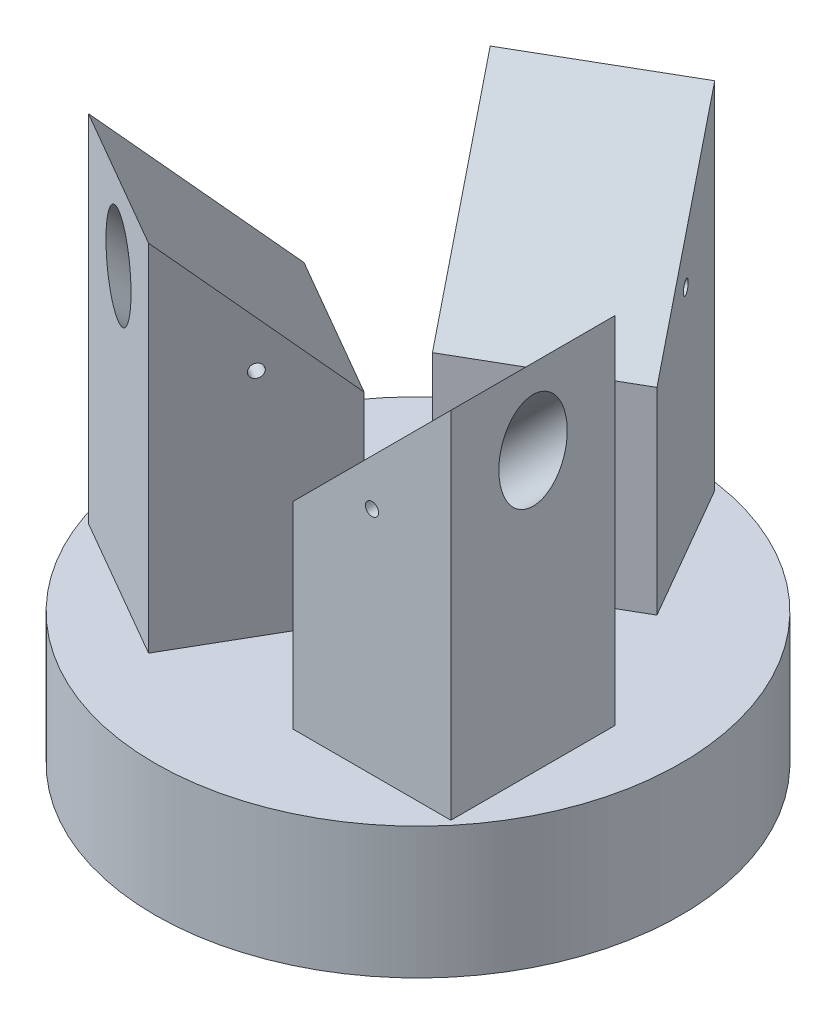
SolidWorks part; units mm, degrees
ref_plane "Front Plane" through (0, 0, 0) normal (0, 0, 1) x (1, 0, 0)
ref_plane "Top Plane" through (0, 0, 0) normal (0, 1, 0) x (1, 0, 0)
ref_plane "Right Plane" through (0, 0, 0) normal (1, 0, 0) x (0, 0, -1)
sketch "Sketch1" plane through (0, 0, 0) normal (0, 1, 0) x (1, 0, 0)
  circle A0 centre (0, 0) radius 50.8
  dimension "D1" = 101.6
extrude "Boss-Extrude1" add sketch "Sketch1" along normal blind 25.4
ref_axis "Axis1" through (0, 25.4, 0) along (0, -1, 0)
sketch "Sketch3" plane through (0, 25.4, 0) normal (0, 1, 0) x (1, 0, 0)
  line L0 (0, 0) -> (50.8, 0)
  circle A0 centre (0, 0) radius 50.8 construction
ref_plane "Plane1" through (0, 0, 0) normal (0, 0, 1) x (1, 0, 0)
sketch "Sketch4" plane through (0, 0, 0) normal (0, 0, 1) x (1, 0, 0)
  line L0 (7.62, 25.4) -> (7.62, 63.5)
  line L1 (38.1, 25.4) -> (7.62, 25.4)
  line L2 (38.1, 25.4) -> (38.1, 93.98)
  line L3 (38.1, 93.98) -> (7.62, 63.5)
  line L4 (7.62, 63.5) -> (52.1327, 63.5) construction
  dimension "D1" = 45
extrude "Boss-Extrude2" add sketch "Sketch4" along normal blind 31.75
sketch "Sketch5" plane through (38.1, 0, 0) normal (1, 0, 0) x (0, 0, -1)
  line L0 (-15.875, 93.98) -> (-15.875, 81.28) construction
  line L1 (-31.75, 93.98) -> (0, 93.98) construction
  line L2 (-15.875, 95.504) -> (-2.6499, 95.504)
  circle A0 centre (-15.875, 81.28) radius 14.224
  dimension "D1" = 12.7
ref_plane "Plane2" through (66.802, 66.802, 0) normal (0.7071, 0.7071, 0) x (0, 0, -1)
sketch "Sketch7" plane through (7.62, 0, 0) normal (-1, 0, 0) x (0, 0, 1)
  line L0 (15.875, 63.5) -> (15.875, 50.8) construction
  line L1 (31.75, 63.5) -> (0, 63.5) construction
  line L3 (15.875, 57.404) -> (28.7041, 57.404)
  circle A0 centre (15.875, 50.8) radius 6.604
  dimension "D1" = 12.7
ref_plane "Plane3" through (32.512, 32.512, 0) normal (-0.7071, -0.7071, 0) x (0, 0, 1)
sketch "Sketch9" plane through (66.802, 66.802, 0) normal (0.7071, 0.7071, 0) x (0, 0, -1)
  line L0 (-15.875, 40.5908) -> (-15.875, 29.1608) construction
  circle A0 centre (-15.875, 29.1608) radius 6.604
  dimension "D1" = 11.43
extrude "Cut-Extrude2" cut sketch "Sketch9" against normal blind 68.58
sketch "Sketch10" plane through (0, 0, 31.75) normal (0, 0, 1) x (1, 0, 0)
  line L0 (22.86, 78.74) -> (22.86, 69.85) construction
  line L1 (38.1, 93.98) -> (7.62, 63.5) construction
  circle A0 centre (22.86, 69.85) radius 1.27
extrude "Cut-Extrude3" cut sketch "Sketch10" against normal blind 68.58
pattern_circular "CirPattern3" count 3 over 360 about axis through (0, 25.4, 0) along (0, -1, 0) of "Boss-Extrude2", "Cut-Extrude3", "Cut-Extrude2"
sketch "Sketch11" plane through (0, 25.4, 0) normal (0, 1, 0) x (1, 0, 0)
  circle A0 centre (0, 0) radius 4.7625
  dimension "D1" = 9.525
extrude "Cut-Extrude4" cut sketch "Sketch11" against normal up to surface (25.4 mm away) up to face at (0, 0, 50.8)
